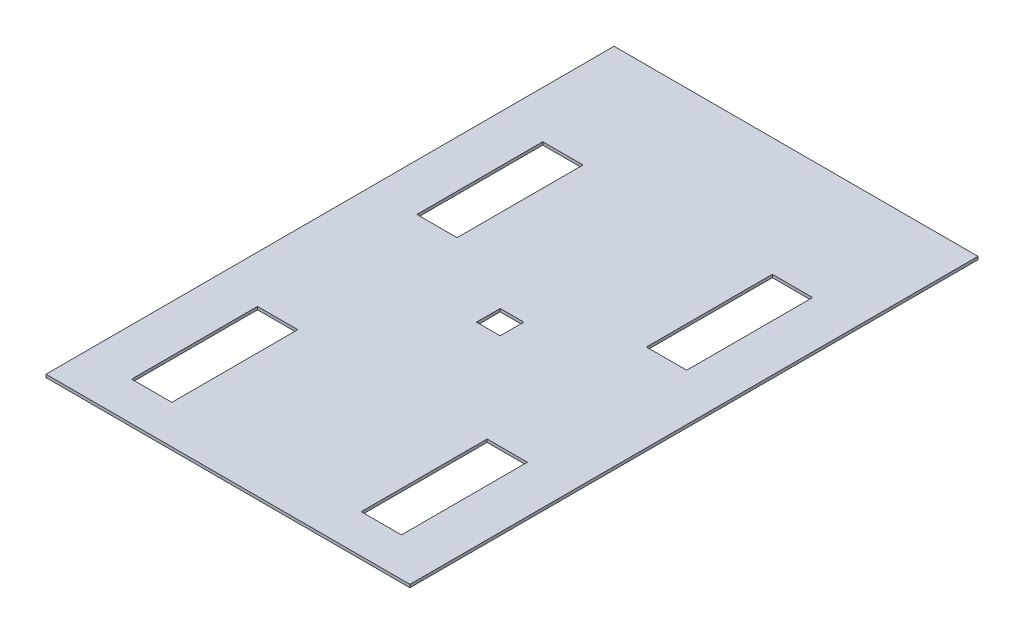
SolidWorks part; units mm, degrees
ref_plane "Front Plane" through (0, 0, 0) normal (0, 0, 1) x (1, 0, 0)
ref_plane "Top Plane" through (0, 0, 0) normal (0, 1, 0) x (1, 0, 0)
ref_plane "Right Plane" through (0, 0, 0) normal (1, 0, 0) x (0, 0, -1)
sketch "Sketch1" plane through (0, 0, 0) normal (0, 1, 0) x (1, 0, 0)
  line L1 (-195.2625, -304.8) -> (195.2625, -304.8)
  line L2 (-195.2625, -304.8) -> (-195.2625, 304.8)
  line L3 (-195.2625, 304.8) -> (195.2625, 304.8)
  line L4 (195.2625, -304.8) -> (195.2625, 304.8)
  line L5 (0, 304.8) -> (0, -304.8) construction
  line L6 (-195.2625, 0) -> (195.2625, 0) construction
  point P0 (0, 0)
  dimension "D1" = 390.525
  dimension "D2" = 609.6
extrude "Boss-Extrude1" add sketch "Sketch1" along normal blind 3.175
sketch "Sketch2" plane through (0, 3.175, 0) normal (0, 1, 0) x (1, 0, 0)
  line L0 (0, -1000) -> (0, 49000) construction
  line L5 (195.2625, 304.8) -> (-195.2625, 304.8) construction
  line L6 (101.6, -263.4234) -> (144.78, -263.4234)
  line L7 (101.6, 42.672) -> (144.78, 42.672)
  line L8 (101.6, 42.672) -> (101.6, 177.8)
  line L9 (101.6, 177.8) -> (144.78, 177.8)
  line L10 (144.78, 42.672) -> (144.78, 177.8)
  line L11 (123.19, 177.8) -> (123.19, 42.672) construction
  line L12 (101.6, 110.236) -> (144.78, 110.236) construction
  line L17 (101.6, -263.4234) -> (101.6, -128.2954)
  line L18 (101.6, -128.2954) -> (144.78, -128.2954)
  line L23 (144.78, -263.4234) -> (144.78, -128.2954)
  line L24 (123.19, -128.2954) -> (123.19, -263.4234) construction
  line L25 (101.6, -195.8594) -> (144.78, -195.8594) construction
  line L26 (-123.19, -128.2954) -> (-123.19, -263.4234) construction
  line L27 (-144.78, -263.4234) -> (-144.78, -128.2954)
  line L28 (-101.6, -263.4234) -> (-101.6, -128.2954)
  line L29 (-101.6, -263.4234) -> (-144.78, -263.4234)
  line L30 (-101.6, -195.8594) -> (-144.78, -195.8594) construction
  line L31 (-101.6, -128.2954) -> (-144.78, -128.2954)
  line L32 (-101.6, 110.236) -> (-144.78, 110.236) construction
  line L33 (-123.19, 177.8) -> (-123.19, 42.672) construction
  line L34 (-144.78, 42.672) -> (-144.78, 177.8)
  line L35 (-101.6, 177.8) -> (-144.78, 177.8)
  line L36 (-101.6, 42.672) -> (-101.6, 177.8)
  line L37 (-101.6, 42.672) -> (-144.78, 42.672)
  point P1 (123.19, -195.8594)
  point P4 (123.19, 110.236)
  point P20 (-123.19, -195.8594)
  point P29 (-123.19, 110.236)
  dimension "D1" = 135.128
  dimension "D2" = 43.18
  dimension "D3" = 135.128
  dimension "D4" = 306.0954
  dimension "D5" = 127
  dimension "D6" = 123.19
extrude "Cut-Extrude1" cut sketch "Sketch2" against normal through all
sketch "Sketch4" plane through (0, 0, 0) normal (0, 1, 0) x (1, 0, 0)
  line L5 (144.78, 177.8) -> (101.6, 177.8) construction
  line L6 (-12.7, -25.4) -> (12.7, -25.4)
  line L7 (-12.7, -25.4) -> (-12.7, 0)
  line L8 (-12.7, 0) -> (12.7, 0)
  line L9 (12.7, -25.4) -> (12.7, 0)
  line L10 (0, 0) -> (0, -25.4) construction
  line L11 (-12.7, -12.7) -> (12.7, -12.7) construction
  point P0 (0, -12.7)
  dimension "D1" = 25.4
  dimension "D2" = 177.8
  dimension "D3" = 25.4
extrude "Cut-Extrude3" cut sketch "Sketch4" along normal through all
